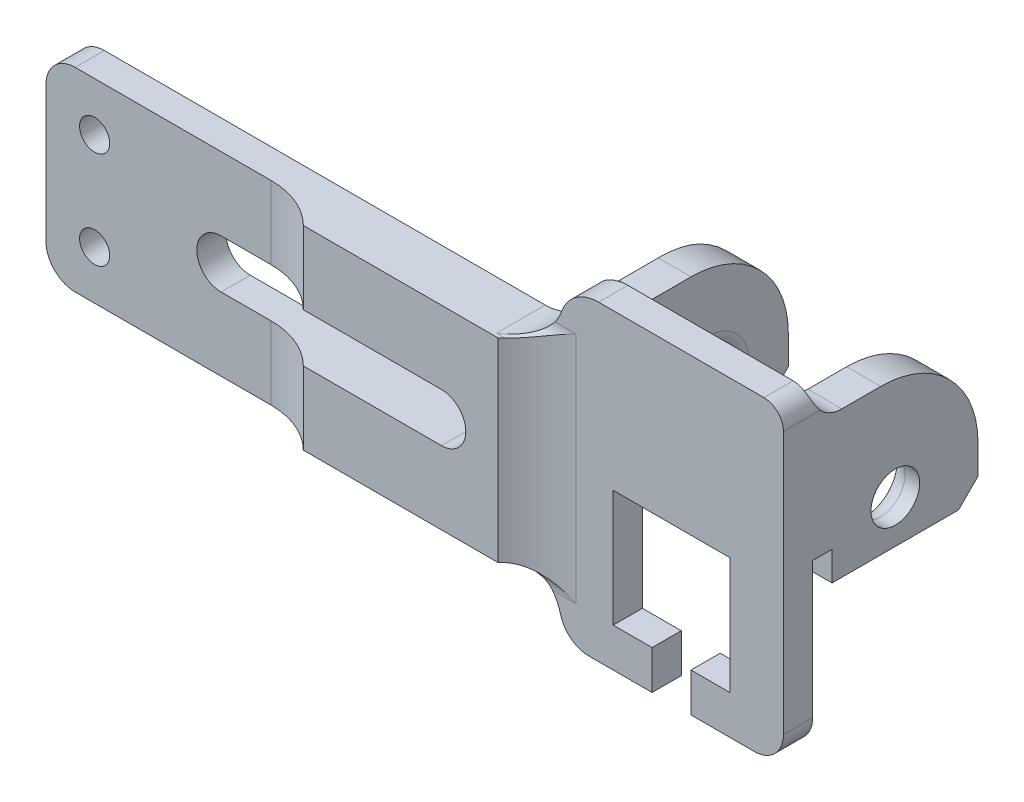
SolidWorks part; units mm, degrees
ref_plane "Alzado" through (0, 0, 0) normal (0, 0, 1) x (1, 0, 0)
ref_plane "Planta" through (0, 0, 0) normal (0, 1, 0) x (1, 0, 0)
ref_plane "Vista lateral" through (0, 0, 0) normal (1, 0, 0) x (0, 0, -1)
sketch "Croquis1" plane through (0, 0, 0) normal (0, 1, 0) x (1, 0, 0)
  line L0 (0, 2.5) -> (30.8, 2.5) construction
  line L1 (0, 0) -> (30.8, 0)
  line L2 (0, 0) -> (0, 5)
  line L3 (0, 5) -> (30.8, 5)
  line L4 (30.8, 0) -> (30.8, 5)
  circle A0 centre (3, 2.5) radius 1.6
  circle A1 centre (25, 2.5) radius 1.6
  dimension "D2" = 3.2
  dimension "D5" = 3.2
  dimension "D1" = 5
  dimension "D3" = 3
  dimension "D4" = 30.8
  dimension "D6" = 22
extrude "Saliente-Extruir1" add sketch "Croquis1" along normal blind 2.5
sketch "Croquis2" plane through (0, 0, 0) normal (0, -1, 0) x (1, 0, 0)
  line L1 (30.8, 0) -> (28.3, 0)
  line L2 (30.8, 0) -> (30.8, -24)
  line L3 (30.8, -24) -> (28.3, -24)
  line L4 (28.3, 0) -> (28.3, -24)
  dimension "D1" = 2.5
  dimension "D2" = 24
extrude "Saliente-Extruir2" add sketch "Croquis2" along normal blind 10
sketch "Croquis3" plane through (28.3, 0, 0) normal (-1, 0, 0) x (0, 0, 1)
  line L0 (-5, 0) -> (-24, 0) construction
  line L1 (-24, -10) -> (-21, -10)
  line L2 (-24, -10) -> (-24, 0)
  line L3 (-24, 0) -> (-21, 0)
  line L4 (-21, -10) -> (-21, 0)
  dimension "D1" = 3
extrude "Saliente-Extruir3" add sketch "Croquis3" along normal blind 20.5
sketch "Croquis4" plane through (0, -10, 0) normal (0, -1, 0) x (1, 0, 0)
  line L1 (30.8, -24) -> (7.8, -24)
  line L2 (30.8, -24) -> (30.8, -21)
  line L3 (30.8, -21) -> (7.8, -21)
  line L4 (7.8, -24) -> (7.8, -21)
extrude "Saliente-Extruir4" add sketch "Croquis4" along normal blind 45
sketch "Croquis6" plane through (0, 0, -24) normal (0, 0, -1) x (-1, 0, 0)
  line L1 (-30.8, -32) -> (-27.3, -32)
  line L2 (-30.8, -32) -> (-30.8, -17)
  line L3 (-30.8, -17) -> (-27.3, -17)
  line L4 (-27.3, -32) -> (-27.3, -17)
  line L5 (-7.8, -32) -> (-11.3, -32)
  line L6 (-7.8, -32) -> (-7.8, -17)
  line L7 (-7.8, -17) -> (-11.3, -17)
  line L8 (-11.3, -32) -> (-11.3, -17)
  line L9 (-7.8, -55) -> (-30.8, -55) construction
  line L10 (-30.8, -55) -> (-30.8, 0) construction
  line L11 (-7.8, 0) -> (-7.8, -55) construction
  point P16 (-29.05, -32)
  dimension "D1" = 3.5
  dimension "D2" = 15
  dimension "D3" = 15
  dimension "D4" = 3.5
  dimension "D5" = 23
extrude "Saliente-Extruir6" add sketch "Croquis6" along normal blind 17
sketch "Croquis7" plane through (11.3, 0, 0) normal (1, 0, 0) x (0, 0, -1)
  line L2 (41, -17) -> (41, -32) construction
  line L3 (41, -32) -> (24, -32) construction
  circle A0 centre (32.5, -27.6) radius 2.5
  dimension "D1" = 5
  dimension "D2" = 4.4
  dimension "D3" = 8.5
extrude "Cortar-Extruir1" cut sketch "Croquis7" against normal up to surface and the other way up to surface up to face at (7.8, -26, -27.5) other way up to face at (30.8, -18.5833, -19.1667)
fillet "Redondeo1" radius 2 2 edges at (27.3, -27.6, -35) (11.3, -30.1, -32.5)
sketch "Croquis8" plane through (0, 0, -5) normal (0, 0, -1) x (-1, 0, 0)
  line L1 (-30.8, 2.5) -> (-7.8, 2.5)
  line L2 (-30.8, 2.5) -> (-30.8, 0)
  line L3 (-30.8, 0) -> (-7.8, 0)
  line L4 (-7.8, 2.5) -> (-7.8, 0)
extrude "Saliente-Extruir7" add sketch "Croquis8" along normal up to surface (19 mm away) up to face at (19.3, -25.5, -24)
sketch "Croquis9" plane through (30.8, 0, 0) normal (1, 0, 0) x (0, 0, -1)
  line L0 (24, -17) -> (24, 2.5) construction
  line L1 (0, -10) -> (21, -10)
  line L2 (0, -10) -> (0, 0)
  line L3 (0, 0) -> (21, 0)
  line L4 (21, -10) -> (21, 0)
  line L5 (0, 2.5) -> (24, 2.5) construction
  dimension "D1" = 3
  dimension "D2" = 2.5
extrude "Cortar-Extruir2" cut sketch "Croquis9" against normal up to surface (2.5 mm away) up to face at (28.3, -5, -10.5)
sketch "Croquis11" plane through (0, 0, -24) normal (0, 0, -1) x (-1, 0, 0)
  line L0 (-11.3, -17) -> (-11.3, -32) construction
  line L1 (-13.3, -30) -> (-25.3, -30)
  line L2 (-13.3, -30) -> (-13.3, -42)
  line L3 (-13.3, -42) -> (-25.3, -42)
  line L4 (-25.3, -30) -> (-25.3, -42)
  line L5 (-27.3, -32) -> (-27.3, -17) construction
  line L6 (-7.8, -55) -> (-30.8, -55) construction
  dimension "D1" = 2
  dimension "D2" = 12
  dimension "D3" = 2
  dimension "D4" = 13
extrude "Cortar-Extruir3" cut sketch "Croquis11" against normal up to surface (3 mm away) up to face at (19.3, -27.5, -21)
sketch "Croquis13" plane through (0, 0, -24) normal (0, 0, -1) x (-1, 0, 0)
  line L0 (-7.8, -32) -> (-7.8, -55) construction
  line L1 (-30.8, -55) -> (-7.8, -55)
  line L2 (-30.8, -55) -> (-30.8, -46)
  line L3 (-30.8, -46) -> (-21.3, -46)
  line L4 (-7.8, -55) -> (-7.8, -46)
  line L5 (-25.3, -42) -> (-13.3, -42) construction
  line L6 (-30.8, -55) -> (-30.8, -32) construction
  line L7 (-21.3, -42) -> (-17.3, -42)
  line L8 (-21.3, -42) -> (-21.3, -46)
  line L10 (-17.3, -42) -> (-17.3, -46)
  line L11 (-17.3, -46) -> (-7.8, -46)
  dimension "D1" = 4
  dimension "D2" = 4
  dimension "D3" = 9.5
extrude "Cortar-Extruir5" cut sketch "Croquis13" against normal up to surface (3 mm away) up to face at (19.3, -36, -21)
fillet "Redondeo7" radius 3 4 edges at (7.8, -46, -22.5) (30.8, -46, -22.5) (9.55, -17, -24) (29.05, -17, -24)
sketch "Croquis15" plane through (0, -32, 0) normal (0, -1, 0) x (1, 0, 0)
  line L0 (30.8, -41) -> (30.8, -24) construction
  line L1 (30.8, -26) -> (7.8, -26)
  line L2 (30.8, -26) -> (30.8, -24)
  line L3 (30.8, -24) -> (7.8, -24)
  line L4 (7.8, -26) -> (7.8, -24)
  line L5 (7.8, -41) -> (7.8, -24) construction
  line L6 (11.3, -24) -> (7.8, -24) construction
  dimension "D1" = 2
extrude "Cortar-Extruir7" cut sketch "Croquis15" against normal blind 3
fillet "Redondeo9" radius 10 2 edges at (9.55, -17, -41) (29.05, -17, -41)
chamfer "Chaflán2" distance 2 angle 45 2 edges at (29.05, -32, -41) (9.55, -32, -41)
sketch "Croquis16" plane through (30.8, 0, 0) normal (1, 0, 0) x (0, 0, -1)
  line L1 (21, 0) -> (0, 0)
  line L2 (21, 0) -> (21, 2.5)
  line L3 (21, 2.5) -> (0, 2.5)
  line L4 (0, 0) -> (0, 2.5)
extrude "Cortar-Extruir8" cut sketch "Croquis16" against normal up to surface (30.8 mm away) up to face at (0, 1.25, -2.5)
sketch "Croquis17" plane through (7.8, 0, 0) normal (-1, 0, 0) x (0, 0, 1)
  line L0 (-24, -29) -> (-24, -43) construction
  line L1 (-24, -40) -> (-21, -40)
  line L2 (-24, -40) -> (-24, -20)
  line L3 (-24, -20) -> (-21, -20)
  line L4 (-21, -40) -> (-21, -20)
  line L5 (-21, -43) -> (-21, 2.5) construction
  line L6 (-21, -46) -> (-24, -46) construction
  point P10 (-22.5, -46)
  dimension "D1" = 20
  dimension "D2" = 6
extrude "Saliente-Extruir8" add sketch "Croquis17" along normal blind 52.8
sketch "Croquis18" plane through (0, 0, -24) normal (0, 0, -1) x (-1, 0, 0)
  line L0 (45, -20) -> (45, -40) construction
  line L2 (45, -40) -> (-7.8, -40) construction
  circle A1 centre (40, -35) radius 1.55
  circle A2 centre (40, -25) radius 1.55
  dimension "D1" = 3.1
  dimension "D2" = 3.1
  dimension "D3" = 10
  dimension "D4" = 5
  dimension "D5" = 5
extrude "Cortar-Extruir9" cut sketch "Croquis18" against normal up to surface (3 mm away) up to face at (10.8778, -34.1246, -21)
sketch "Croquis19" plane through (0, 0, -24) normal (0, 0, -1) x (-1, 0, 0)
  line L1 (-7.8, 2.5) -> (-30.8, 2.5)
  line L2 (-7.8, 2.5) -> (-7.8, -14)
  line L3 (-7.8, -14) -> (-30.8, -14)
  line L4 (-30.8, 2.5) -> (-30.8, -14)
extrude "Cortar-Extruir10" cut sketch "Croquis19" against normal up to surface (3 mm away) up to face at (-41.55, -25, -21)
fillet "Redondeo11" radius 3 2 edges at (-45, -20, -22.5) (-45, -40, -22.5)
fillet "Redondeo12" radius 4 1 edges at (7.8, -14, -22.5)
fillet "Redondeo13" radius 5 2 edges at (7.8, -40, -22.5) (7.8, -20, -22.5)
sketch "Croquis20" plane through (0, 0, -21) normal (0, 0, 1) x (1, 0, 0)
  line L0 (-42, -20) -> (3.3147, -20) construction
  line L1 (-42, -40) -> (3.054, -40) construction
  line L2 (3.8, -20) -> (-16.2, -20)
  line L3 (3.8, -20) -> (3.8, -40)
  line L4 (3.8, -40) -> (-16.2, -40)
  line L5 (-16.2, -20) -> (-16.2, -40)
  line L6 (30.8, -43) -> (30.8, -14) construction
  dimension "D1" = 27
  dimension "D2" = 20
extrude "Saliente-Extruir9" add sketch "Croquis20" along normal blind 2.35
sketch "Croquis21" plane through (0, 0, -24) normal (0, 0, -1) x (-1, 0, 0)
  circle A0 centre (40, -35) radius 3
  circle A1 centre (40, -25) radius 3
  dimension "D1" = 6
extrude "Cortar-Extruir11" cut sketch "Croquis21" against normal blind 0.5
fillet "Redondeo14" radius 2 1 edges at (30.8, -14, -22.5)
fillet "Redondeo15" radius 8 2 edges at (-16.2, -30, -21) (3.8, -30, -21)
fillet "Redondeo16" radius 2 2 edges at (6.2589, -40, -21) (6.3892, -20, -21)
sketch "Croquis22" plane through (0, 0, -24) normal (0, 0, -1) x (-1, 0, 0)
  line L0 (45, -30) -> (-7.793, -30) construction
  line L1 (45, -23) -> (45, -37) construction
  line L2 (2, -30) -> (27, -30) construction
  line L3 (2, -27.5) -> (27, -27.5)
  line L4 (2, -32.5) -> (27, -32.5)
  arc A0 (2, -27.5) -> (2, -32.5) centre (2, -30) ccw
  arc A1 (27, -32.5) -> (27, -27.5) centre (27, -30) ccw
  point P6 (14.5, -30)
  dimension "D1" = 5
  dimension "D2" = 25
  dimension "D3" = 18
extrude "Cortar-Extruir12" cut sketch "Croquis22" against normal up to surface (5.35 mm away) up to face at (-6.2, -30, -18.65)
fillet "Redondeo17" radius 1.6 2 edges at (7.8576, -17.3236, -24) (7.8, -23.5, -24)
